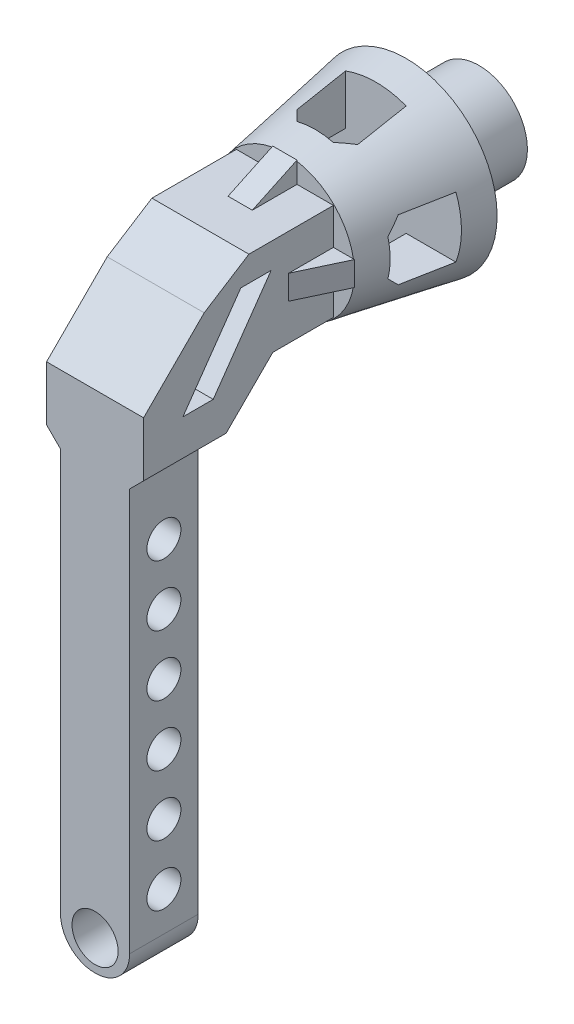
SolidWorks part; units mm, degrees
ref_plane "前视基准面" through (0, 0, 0) normal (0, 0, 1) x (1, 0, 0)
ref_plane "上视基准面" through (0, 0, 0) normal (0, 1, 0) x (1, 0, 0)
ref_plane "右视基准面" through (0, 0, 0) normal (1, 0, 0) x (0, 0, -1)
other "Configuration Table"
sketch "草图1" plane through (0, 0, 0) normal (0, 0, 1) x (1, 0, 0)
  circle A0 centre (0, 0) radius 2.5
  circle A1 centre (0, 0) radius 4
  dimension "D1" = 5
  dimension "D2" = 8
extrude "凸台-拉伸1" add sketch "草图1" along normal blind 6
sketch "草图2" plane through (0, 0, 6) normal (0, 0, 1) x (1, 0, 0)
  circle A0 centre (0, 0) radius 7.5
  dimension "D1" = 15
extrude "凸台-拉伸2" add sketch "草图2" along normal blind 10 draft 10 contours A0
chamfer "倒角1" distance 1 angle 45 1 edges at (2.5, 0, 0)
sketch "草图5" plane through (0, 0, 6) normal (0, 0, -1) x (-1, 0, 0)
  circle A0 centre (0, 0) radius 2.5 construction
  circle A1 centre (0, 0) radius 2.5
curve "螺旋线/涡状线2" pitch 0.8 height 5.6 turns 7
ref_plane "基准面1" through (1.7678, 1.7678, 0.4) normal (-0.7062, 0.7062, -0.0509) x (0.6934, 0.7044, 0.1517)
sketch "草图6" plane through (1.7678, 1.7678, 0.4) normal (-0.7062, 0.7062, -0.0509) x (0.6934, 0.7044, 0.1517)
  line L0 (0.3452, 0.0295) -> (0, 0) construction
  line L1 (-0.017, 0.1993) -> (0.017, -0.1993)
  line L2 (0.017, -0.1993) -> (0.3452, 0.0295)
  line L3 (0.3452, 0.0295) -> (-0.017, 0.1993)
  circle A0 centre (0.1151, 0.0098) radius 0.1155 construction
  dimension "D1" = 0.4
sweep "切除-扫描1" cut profiles "草图6" path "螺旋线/涡状线2"
sketch "草图7" plane through (0, 0, 16) normal (0, 0, 1) x (1, 0, 0)
  line L0 (-1000, 0) -> (-4, 0) construction
  line L3 (4, -4) -> (-4, -4)
  line L4 (-4, 4) -> (-4, -4)
  line L5 (0, 1002.4932) -> (0, 4) construction
  line L6 (4, 4) -> (-4, 4)
  line L7 (4, 4) -> (4, -4)
  line L8 (4, 0) -> (1005.5512, 0) construction
  line L9 (0, -4) -> (0, -1003.4308) construction
  dimension "D1" = 8
extrude "凸台-拉伸5" add sketch "草图7" along normal blind 5
sketch "草图12" plane through (-4, 0, 0) normal (-1, 0, 0) x (0, 0, 1)
  line L0 (21, 4) -> (21, -4)
  line L1 (21, -4) -> (29, 4)
  line L2 (29, 4) -> (21, 4)
  dimension "D1" = 8
extrude "凸台-拉伸6" add sketch "草图12" against normal up to surface (8 mm away) up to face at (4, 0, 18.5)
sketch "草图13" plane through (0, -12.5, 12.5) normal (0, -0.7071, 0.7071) x (1, 0, 0)
  line L0 (4, 23.3345) -> (4, 12.0208) construction
  line L1 (-4, 12.0208) -> (4, 12.0208)
  line L2 (-4, 12.0208) -> (-4, 20.0208)
  line L3 (-4, 20.0208) -> (4, 20.0208)
  line L4 (4, 12.0208) -> (4, 20.0208)
  dimension "D1" = 8
extrude "凸台-拉伸7" add sketch "草图13" along normal blind 7.07
sketch "草图15" plane through (-4, 0, 0) normal (-1, 0, 0) x (0, 0, 1)
  line L0 (31.6561, -3.3424) -> (31.6561, -8.9992)
  line L1 (31.6561, -8.9992) -> (25.9992, -8.9992)
  line L2 (31.6561, -3.3424) -> (25.9992, -8.9992) construction
  line L3 (31.6561, -3.3424) -> (25.9992, -8.9992)
  dimension "D1" = 45
extrude "凸台-拉伸8" add sketch "草图15" against normal up to surface (8 mm away) contours L1 L3 L0 up to face at (4, -1.5264, 23.7589)
sketch "草图16" plane through (0, -8.9992, 0) normal (0, -1, 0) x (1, 0, 0)
  line L0 (-4, 25.9992) -> (4, 25.9992) construction
  line L1 (-2.85, 25.9992) -> (2.85, 25.9992)
  line L2 (-2.85, 25.9992) -> (-2.85, 31.6561)
  line L3 (-2.85, 31.6561) -> (2.85, 31.6561)
  line L4 (2.85, 25.9992) -> (2.85, 31.6561)
  line L5 (4, 31.6561) -> (-4, 31.6561) construction
  line L6 (4, 25.9992) -> (4, 31.6561) construction
  line L7 (-4, 31.6561) -> (-4, 25.9992) construction
  dimension "D1" = 1.15
  dimension "D2" = 1.15
extrude "凸台-拉伸9" add sketch "草图16" along normal blind 31
sketch "草图17" plane through (0, 0, 25.9992) normal (0, 0, -1) x (-1, 0, 0)
  line L0 (0, -39.9992) -> (0, -44.9992) construction
  line L1 (-2.85, -39.9992) -> (2.85, -39.9992)
  line L2 (-2.85, -39.9992) -> (-2.85, -44.9992)
  line L3 (-2.85, -44.9992) -> (2.85, -44.9992)
  line L4 (2.85, -39.9992) -> (2.85, -44.9992)
  line L5 (-2.85, -42.4992) -> (2.85, -42.4992) construction
  circle A0 centre (0, -42.4992) radius 1.9
  dimension "D3" = 3.8
  dimension "D1" = 5.7
  dimension "D2" = 5
extrude "凸台-拉伸10" add sketch "草图17" against normal up to surface (5.6569 mm away) up to face at (0, -15.335, 31.6561)
fillet "圆角1" radius 2.8 2 edges at (-2.85, -44.9992, 28.8277) (2.85, -44.9992, 28.8277)
sketch "草图18" plane through (4, 0, 0) normal (1, 0, 0) x (0, 0, -1)
  line L0 (-26.6569, 1.6569) -> (-22.9688, 4)
  line L1 (-29, 4) -> (-16, 4) construction
  line L2 (-22.9688, 4) -> (-29, 4)
  line L3 (-29, 4) -> (-26.6569, 1.6569)
extrude "切除-拉伸2" cut sketch "草图18" against normal through all
chamfer "倒角2" distance 1.15 angle 45 2 edges at (4, -8.9992, 28.8277) (-4, -8.9992, 28.8277)
sketch "草图19" plane through (0, 0, 0) normal (0, 1, 0) x (1, 0, 0)
  line L0 (-5.7367, -16) -> (-4, -19.6902)
  line L1 (-4, -22.9688) -> (-4, -16) construction
  line L2 (-4, -19.6902) -> (-4, -16)
  line L3 (-4, -16) -> (-5.7367, -16)
  line L4 (4, -16) -> (4, -19.6902)
  line L5 (4, -22.9688) -> (4, -16) construction
  line L6 (4, -19.6902) -> (5.7367, -16)
  line L7 (5.7367, -16) -> (4, -16)
extrude "凸台-拉伸11" add sketch "草图19" along normal blind 1 and the other way blind 1
sketch "草图20" plane through (0, 0, 0) normal (1, 0, 0) x (0, 0, -1)
  line L0 (-19.6902, -4) -> (-16, -5.7367)
  line L1 (-21, -4) -> (-16, -4) construction
  line L2 (-16, -1) -> (-16, -5.7367) construction
  line L3 (-16, -5.7367) -> (-16, -4)
  line L4 (-16, -4) -> (-19.6902, -4)
  line L5 (-19.6902, 4) -> (-16, 5.7367)
  line L6 (-22.9688, 4) -> (-16, 4) construction
  line L7 (-16, 5.7367) -> (-16, 1) construction
  line L8 (-16, 5.7367) -> (-16, 4)
  line L9 (-16, 4) -> (-19.6902, 4)
extrude "凸台-拉伸12" add sketch "草图20" along normal blind 1 and the other way blind 1
sketch "草图21" plane through (0, 0, 0) normal (0, 1, 0) x (1, 0, 0)
  line L0 (0, -6) -> (0, -8.5) construction
  line L1 (7.5, -6) -> (-7.5, -6) construction
  line L2 (-6.6184, -11) -> (-2.5, -11) construction
  line L3 (-7.5, -6) -> (-5.7367, -16) construction
  line L4 (5.7367, -16) -> (7.5, -6) construction
  line L5 (2.5, -13.5) -> (2.5, -8.5)
  line L8 (2.5, -8.5) -> (-2.5, -8.5)
  line L9 (-2.5, -13.5) -> (-2.5, -8.5)
  line L10 (2.5, -13.5) -> (-2.5, -13.5)
  line L11 (0, -13.5) -> (0, -16) construction
  line L12 (2.5, -11) -> (6.6184, -11) construction
extrude "切除-拉伸3" cut sketch "草图21" against normal blind 10 and the other way blind 10
sketch "草图22" plane through (0, 0, 0) normal (1, 0, 0) x (0, 0, -1)
  line L0 (-6, 0) -> (-8.5, 0) construction
  line L1 (-6, -7.5) -> (-6, 7.5) construction
  line L2 (8.25, 0) -> (-8.25, 0) construction
  line L3 (-16, -1) -> (-16, 0) construction
  line L4 (-13.5, -2.5) -> (-8.5, -2.5)
  line L6 (-13.5, -2.5) -> (-13.5, 2.5)
  line L7 (-13.5, 2.5) -> (-8.5, 2.5)
  line L8 (-8.5, -2.5) -> (-8.5, 2.5)
  line L9 (-13.5, 0) -> (-16, 0) construction
  dimension "D1" = 2.5
extrude "切除-拉伸4" cut sketch "草图22" against normal blind 10 and the other way blind 10
chamfer "倒角4" distance 1 angle 45 8 edges at (2.5, -4.0745, 13.5) (4.0745, -2.5, 13.5) (4.0745, 2.5, 13.5) (2.5, 4.0745, 13.5) (-2.5, 4.0745, 13.5) (-4.0745, 2.5, 13.5) (-2.5, -4.0745, 13.5) (-4.0745, -2.5, 13.5)
sketch "草图23" plane through (0, 0, 6) normal (0, 0, -1) x (-1, 0, 0)
  circle A0 centre (0, 0) radius 2.5
  dimension "D1" = 5
extrude "切除-拉伸5" cut sketch "草图23" against normal blind 2
chamfer "倒角5" distance 2 angle 45 1 edges at (-2.5, 0, 8)
sketch "草图24" plane through (-4, 0, 0) normal (-1, 0, 0) x (0, 0, 1)
  line L0 (21.1378, 1.9235) -> (23.6378, 1.9235)
  line L1 (23.6378, 1.9235) -> (28.4139, -4.8976)
  line L2 (28.4139, -4.8976) -> (25.9139, -4.8976)
  line L3 (25.9139, -4.8976) -> (21.1378, 1.9235)
  dimension "D1" = 2.5
  dimension "D2" = 125
  dimension "D3" = 2.5
extrude "切除-拉伸8" cut sketch "草图24" against normal blind 10
sketch "草图26" plane through (2.85, 0, 0) normal (1, 0, 0) x (0, 0, -1)
  line L0 (-28.8277, -8.9992) -> (-28.8277, -44.9992) construction
  line L1 (-25.9992, -8.9992) -> (-31.6561, -8.9992) construction
  line L2 (-25.9992, -44.9992) -> (-31.6561, -44.9992) construction
  line L3 (-28.8277, -13.9992) -> (-28.8277, -18.9992) construction
  circle A0 centre (-28.8277, -13.9992) radius 1.4
  circle A1 centre (-28.8277, -18.9992) radius 1.4
  circle A2 centre (-28.8277, -23.9992) radius 1.4
  circle A3 centre (-28.8277, -28.9992) radius 1.4
  circle A4 centre (-28.8277, -33.9992) radius 1.4
  circle A5 centre (-28.8277, -38.9992) radius 1.4
  dimension "D1" = 2.8
  dimension "D2" = 5
  dimension "D4" = 5
  dimension "D3" = 6
extrude "切除-拉伸9" cut sketch "草图26" against normal blind 10
